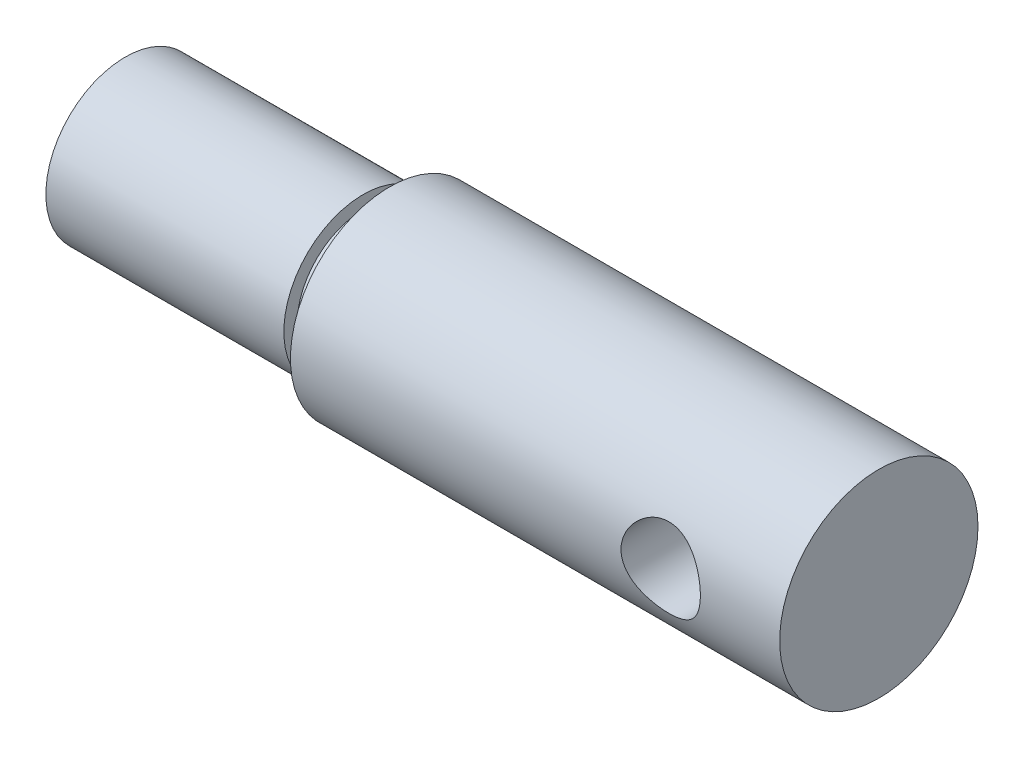
SolidWorks part; units mm, degrees
ref_plane "Front Plane" through (0, 0, 0) normal (0, 0, 1) x (1, 0, 0)
ref_plane "Top Plane" through (0, 0, 0) normal (0, 1, 0) x (1, 0, 0)
ref_plane "Right Plane" through (0, 0, 0) normal (1, 0, 0) x (0, 0, -1)
sketch "Sketch1" plane through (0, 0, 0) normal (0, 0, 1) x (1, 0, 0)
  line L0 (57, 0) -> (0, 0)
  line L1 (0, 0) -> (0, 6)
  line L2 (0, 6) -> (18, 6)
  line L3 (18, 6) -> (18, 5)
  line L4 (18, 5) -> (20, 5)
  line L5 (20, 5) -> (20, 7.5)
  line L6 (20, 7.5) -> (57, 7.5)
  line L7 (57, 7.5) -> (57, 0)
  dimension "D1" = 57
  dimension "D2" = 7.5
  dimension "D3" = 5
  dimension "D4" = 6
  dimension "D5" = 2
  dimension "D6" = 20
revolve "Revolve1" add sketch "Sketch1" angle 360 about L0
cosmetic thread "Cosmetic Thread1" parameters "D2"=10.344
sketch "Sketch2" plane through (0, 0, 0) normal (0, 0, 1) x (1, 0, 0)
  line L0 (57, 0) -> (0, 0) construction
  line L1 (57, -7.5) -> (57, 7.5) construction
  circle A0 centre (48, 0) radius 3
  dimension "D2" = 6
  dimension "D1" = 9
extrude "Cut-Extrude1" cut sketch "Sketch2" against normal through all both and the other way through all
dome "Dome1" faces to dome 1 distance 2 reverse direction no elliptical dome no face at (0, 0, -6) parameters "D1"=2
